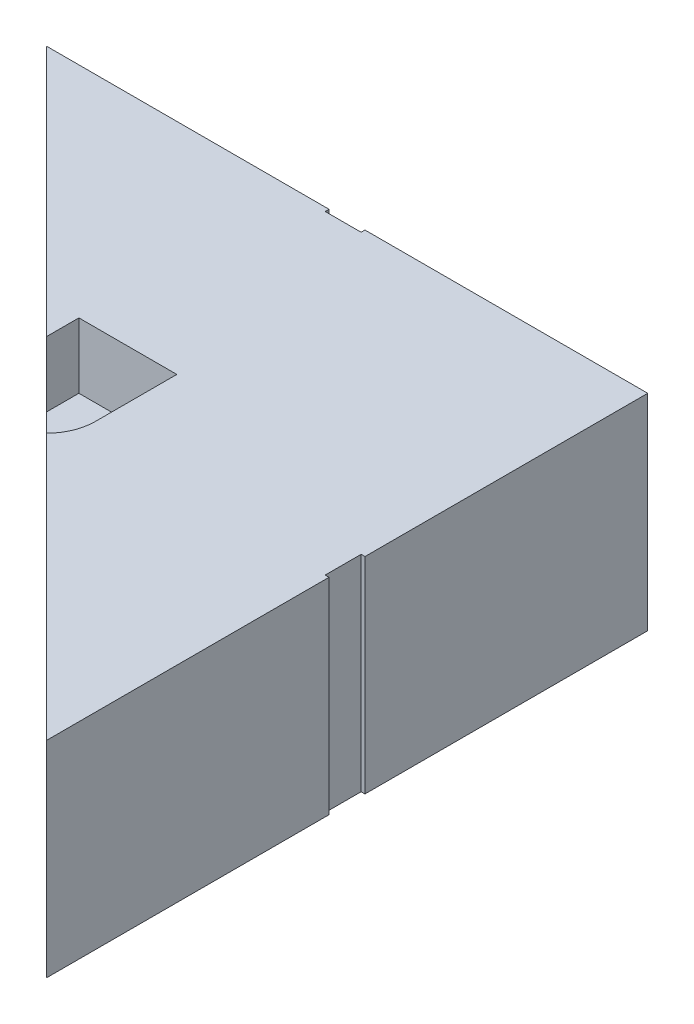
SolidWorks part; units mm, degrees
ref_plane "Front Plane" through (0, 0, 0) normal (0, 0, 1) x (1, 0, 0)
ref_plane "Top Plane" through (0, 0, 0) normal (0, 1, 0) x (1, 0, 0)
ref_plane "Right Plane" through (0, 0, 0) normal (1, 0, 0) x (0, 0, -1)
sketch "Sketch1" plane through (0, 0, 0) normal (0, 1, 0) x (1, 0, 0)
  line L1 (0, 0) -> (117, 0)
  line L2 (0, 0) -> (0, 117)
  line L3 (0, 117) -> (117, 117)
  line L4 (117, 0) -> (117, 117)
  dimension "D1" = 117
  dimension "D2" = 117
extrude "Boss-Extrude1" add sketch "Sketch1" along normal blind 40
sketch "Sketch2" plane through (0, 40, 0) normal (0, 1, 0) x (1, 0, 0)
  line L0 (58.5, 117) -> (58.5, 0) construction
  line L1 (117, 117) -> (0, 117) construction
  line L2 (0, 0) -> (117, 0) construction
  line L3 (0, 58.5) -> (117, 58.5) construction
  line L4 (0, 117) -> (0, 0) construction
  line L5 (117, 0) -> (117, 117) construction
  line L7 (68.025, 58.5) -> (48.975, 58.5)
  line L8 (68.025, 58.5) -> (68.025, 74.375)
  line L9 (68.025, 74.375) -> (48.975, 74.375)
  line L10 (48.975, 58.5) -> (48.975, 74.375)
  line L11 (53.2349, 66.4375) -> (63.7651, 66.4375)
  line L12 (53.2349, 66.4375) -> (53.2349, 50.5625)
  line L13 (53.2349, 50.5625) -> (63.7651, 50.5625)
  line L14 (63.7651, 66.4375) -> (63.7651, 50.5625)
  line L15 (53.2349, 66.4375) -> (63.7651, 50.5625) construction
  line L16 (53.2349, 50.5625) -> (63.7651, 66.4375) construction
  circle A0 centre (58.5, 58.5) radius 9.525
  point P22 (58.5, 50.5625)
  dimension "D1" = 19.05
  dimension "D2" = 19.05
  dimension "D3" = 7.9375
  dimension "D4" = 23.8125
extrude "Cut-Extrude1" cut sketch "Sketch2" against normal blind 12.7 contours A0 L8 L9 L10 | L7 A0 L14 | L12 A0 L7 | L14 L11 L12 L7 | L11 A0 | L14 A0 L7 | L7 A0 L12 | L14 L7 L12 L13
sketch "Sketch4" plane through (0, 0, 0) normal (0, -1, 0) x (1, 0, 0)
  line L0 (0, -117) -> (117, 0)
ref_point "Point1"
ref_axis "Axis1" through (58.5, 0, -58.5) along (0, -1, 0)
sketch "Sketch7" plane through (0, 0, 0) normal (0, -1, 0) x (1, 0, 0)
  line L5 (117, -117) -> (0, -117) construction
  line L10 (55, -116.25) -> (62, -116.25)
  line L11 (55, -116.25) -> (55, -117.75)
  line L12 (55, -117.75) -> (62, -117.75)
  line L13 (62, -116.25) -> (62, -117.75)
  line L14 (55, -116.25) -> (62, -117.75) construction
  line L15 (55, -117.75) -> (62, -116.25) construction
  point P0 (58.5, -117)
  dimension "D1" = 7
  dimension "D2" = 1.5
extrude "Cut-Extrude5" cut sketch "Sketch7" against normal through all
pattern_circular "CirPattern3" count 3 every 90 about axis through (58.5, 0, -58.5) along (0, -1, 0) of "Cut-Extrude5"
sketch "Sketch11" plane through (0, 0, 0) normal (0, -1, 0) x (1, 0, 0)
  line L0 (0, -117) -> (117, 0)
  line L1 (0, -117) -> (-62.346, -54.654)
  line L2 (117, 0) -> (54.654, 62.346)
  line L3 (-62.346, -54.654) -> (54.654, 62.346)
extrude "Cut-Extrude12" cut sketch "Sketch11" against normal through all
